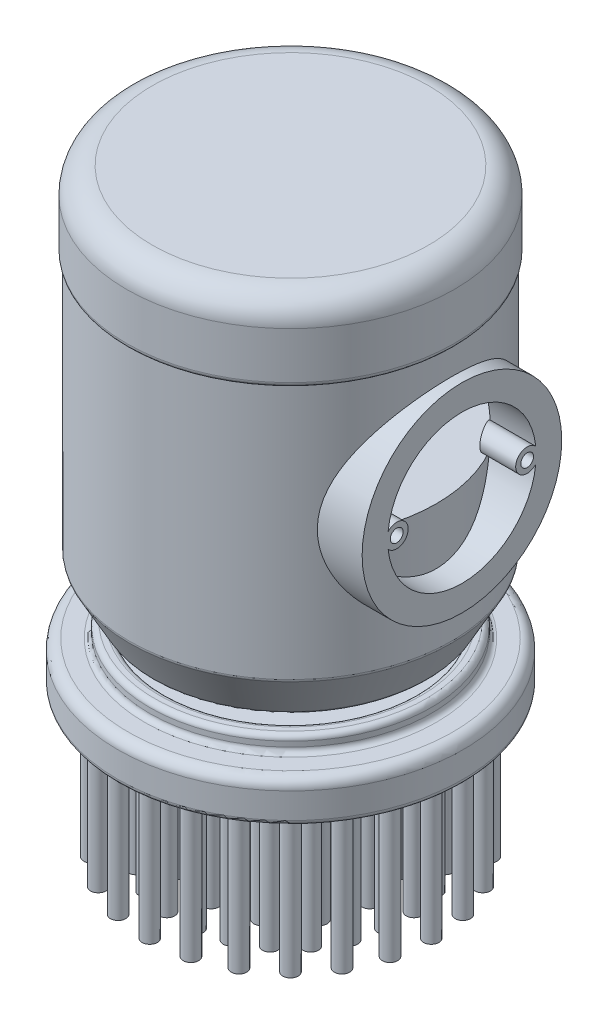
SolidWorks part; units mm, degrees
ref_plane "Front Plane" through (0, 0, 0) normal (0, 0, 1) x (1, 0, 0)
ref_plane "Top Plane" through (0, 0, 0) normal (0, 1, 0) x (1, 0, 0)
ref_plane "Right Plane" through (0, 0, 0) normal (1, 0, 0) x (0, 0, -1)
sketch "Sketch1" plane through (0, 0, 0) normal (0, 0, 1) x (1, 0, 0)
  line L0 (26.5, 0) -> (31.5, 9)
  line L1 (0, 0) -> (31.5, 0)
  line L2 (0, 0) -> (0, 74)
  line L3 (0, 74) -> (31.5, 74)
  line L4 (31.5, 0) -> (31.5, 74)
  line L6 (0, 0) -> (1.5, 0)
  line L7 (0, 0) -> (0, -3)
  line L8 (0, -3) -> (1.5, -3)
  line L9 (1.5, 0) -> (1.5, -3)
  line L10 (0, -3) -> (27.5, -3)
  line L11 (0, -3) -> (0, -6)
  line L12 (0, -6) -> (27.5, -6)
  line L13 (27.5, -3) -> (27.5, -6)
  line L14 (0, -6) -> (33.75, -6)
  line L15 (0, -6) -> (0, -14)
  line L16 (0, -14) -> (33.75, -14)
  line L17 (33.75, -6) -> (33.75, -14)
  dimension "D1" = 31.5
  dimension "D2" = 26.5
  dimension "D3" = 74
  dimension "D4" = 9
  dimension "D5" = 3
  dimension "D6" = 1.5
  dimension "D7" = 27.5
  dimension "D8" = 3
  dimension "D9" = 33.75
  dimension "D10" = 8
revolve "Revolve1" add sketch "Sketch1" angle 360 about L2 region at (15.6127, 37.3314, 0) region at (0.75, -1.5, 0) region at (13.75, -4.5, 0) region at (16.875, -10, 0)
sketch "Sketch2" plane through (0, -3, 0) normal (0, 1, 0) x (1, 0, 0)
  circle A0 centre (0, 0) radius 24.5
  circle A2 centre (0, 0) radius 13
  circle A3 centre (0, 0) radius 27.5 construction
  dimension "D1" = 3
  dimension "D2" = 26
extrude "Cut-Extrude2" cut sketch "Sketch2" against normal blind 2
sketch "Sketch5" plane through (0, 0, 0) normal (1, 0, 0) x (0, 0, -1)
  line L1 (31.5, 74) -> (-31.5, 74) construction
  circle A0 centre (0, 34.5) radius 19.5
  dimension "D1" = 39
  dimension "D2" = 39.5
extrude "Boss-Extrude3" add sketch "Sketch5" along normal blind 33.5
sketch "Sketch7" plane through (0, 74, 0) normal (0, 1, 0) x (1, 0, 0)
  circle A0 centre (0, 0) radius 28.5
  circle A1 centre (0, 0) radius 31.5 construction
  dimension "D1" = 3
extrude "Cut-Extrude3" cut sketch "Sketch7" against normal blind 43
sketch "Sketch3" plane through (0, 74, 0) normal (0, 1, 0) x (1, 0, 0)
  circle A0 centre (0, 0) radius 32
  dimension "D1" = 64
extrude "Boss-Extrude1" add sketch "Sketch3" against normal blind 15
sketch "Sketch4" plane through (0, -14, 0) normal (0, -1, 0) x (1, 0, 0)
  line L0 (0, 27.5) -> (0, 0) construction
  line L1 (0, 0) -> (7.1175, 26.563) construction
  line L2 (3.5895, 27.2647) -> (0, 0) construction
  line L3 (0, 21.6855) -> (2.8063, 21.3161)
  line L4 (2.8063, 21.3161) -> (5.6126, 20.9466)
  line L5 (0, 0) -> (2.8063, 21.3161) construction
  line L6 (0, 0) -> (8.2277, 19.8634) construction
  circle A0 centre (0, 0) radius 27.5 construction
  circle A1 centre (0, 27.5) radius 1.5
  circle A2 centre (0, 0) radius 21.5 construction
  circle A3 centre (0, 0) radius 15.5 construction
  circle A4 centre (0, 15.5) radius 1.5
  circle A5 centre (7.1175, 26.563) radius 1.5
  circle A6 centre (13.75, 23.8157) radius 1.5
  circle A7 centre (19.4454, 19.4454) radius 1.5
  circle A8 centre (23.8157, 13.75) radius 1.5
  circle A9 centre (26.563, 7.1175) radius 1.5
  circle A10 centre (27.5, 0) radius 1.5
  circle A11 centre (26.563, -7.1175) radius 1.5
  circle A12 centre (23.8157, -13.75) radius 1.5
  circle A13 centre (19.4454, -19.4454) radius 1.5
  circle A14 centre (13.75, -23.8157) radius 1.5
  circle A15 centre (7.1175, -26.563) radius 1.5
  circle A16 centre (0, -27.5) radius 1.5
  circle A17 centre (-7.1175, -26.563) radius 1.5
  circle A18 centre (-13.75, -23.8157) radius 1.5
  circle A19 centre (-19.4454, -19.4454) radius 1.5
  circle A20 centre (-23.8157, -13.75) radius 1.5
  circle A21 centre (-26.563, -7.1175) radius 1.5
  circle A22 centre (-27.5, 0) radius 1.5
  circle A23 centre (-26.563, 7.1175) radius 1.5
  circle A24 centre (-23.8157, 13.75) radius 1.5
  circle A25 centre (-19.4454, 19.4454) radius 1.5
  circle A26 centre (2.8063, 21.3161) radius 1.5
  circle A27 centre (0, 0) radius 9.5 construction
  circle A28 centre (-13.75, 23.8157) radius 1.5
  circle A29 centre (-7.1175, 26.563) radius 1.5
  circle A30 centre (8.2277, 19.8634) radius 1.5
  circle A31 centre (13.0884, 17.0571) radius 1.5
  circle A32 centre (17.0571, 13.0884) radius 1.5
  circle A33 centre (19.8634, 8.2277) radius 1.5
  circle A34 centre (21.3161, 2.8063) radius 1.5
  circle A35 centre (21.3161, -2.8063) radius 1.5
  circle A36 centre (19.8634, -8.2277) radius 1.5
  circle A37 centre (17.0571, -13.0884) radius 1.5
  circle A38 centre (13.0884, -17.0571) radius 1.5
  circle A39 centre (8.2277, -19.8634) radius 1.5
  circle A40 centre (2.8063, -21.3161) radius 1.5
  circle A41 centre (-2.8063, -21.3161) radius 1.5
  circle A42 centre (-8.2277, -19.8634) radius 1.5
  circle A43 centre (-13.0884, -17.0571) radius 1.5
  circle A44 centre (-17.0571, -13.0884) radius 1.5
  circle A45 centre (-19.8634, -8.2277) radius 1.5
  circle A46 centre (-21.3161, -2.8063) radius 1.5
  circle A47 centre (-21.3161, 2.8063) radius 1.5
  circle A48 centre (-19.8634, 8.2277) radius 1.5
  circle A49 centre (-17.0571, 13.0884) radius 1.5
  circle A50 centre (-13.0884, 17.0571) radius 1.5
  circle A51 centre (-8.2277, 19.8634) radius 1.5
  circle A52 centre (-2.8063, 21.3161) radius 1.5
  circle A53 centre (4.0117, 14.9719) radius 1.5
  circle A54 centre (7.75, 13.4234) radius 1.5
  circle A55 centre (10.9602, 10.9602) radius 1.5
  circle A56 centre (13.4234, 7.75) radius 1.5
  circle A57 centre (14.9719, 4.0117) radius 1.5
  circle A58 centre (15.5, 0) radius 1.5
  circle A59 centre (14.9719, -4.0117) radius 1.5
  circle A60 centre (13.4234, -7.75) radius 1.5
  circle A61 centre (10.9602, -10.9602) radius 1.5
  circle A62 centre (7.75, -13.4234) radius 1.5
  circle A63 centre (4.0117, -14.9719) radius 1.5
  circle A64 centre (0, -15.5) radius 1.5
  circle A65 centre (-4.0117, -14.9719) radius 1.5
  circle A66 centre (-7.75, -13.4234) radius 1.5
  circle A67 centre (-10.9602, -10.9602) radius 1.5
  circle A68 centre (-13.4234, -7.75) radius 1.5
  circle A69 centre (-14.9719, -4.0117) radius 1.5
  circle A70 centre (-15.5, 0) radius 1.5
  circle A71 centre (-14.9719, 4.0117) radius 1.5
  circle A72 centre (-13.4234, 7.75) radius 1.5
  circle A73 centre (-10.9602, 10.9602) radius 1.5
  circle A74 centre (-7.75, 13.4234) radius 1.5
  circle A75 centre (-4.0117, 14.9719) radius 1.5
  point P54 (0, 0)
  point P159 (0, 0)
  dimension "D1" = 6
  dimension "60" = 55
  dimension "D2" = 3
  dimension "D3" = 6
  dimension "D4" = 3
  dimension "D6" = 3
  dimension "D7" = 6
  dimension "D9" = 15
  dimension "D5" = 24
  dimension "D8" = 24
  dimension "D10" = 24
extrude "Boss-Extrude2" add sketch "Sketch4" along normal blind 29 contours A10 | A9 | A8 | A7 | A6 | A5 | A1 | A29 | A28 | A25 | A24 | A23 | A22 | A21 | A20 | A19 | A18 | A16 | A15 | A14 | A13 | A12 | A11 | A52 | A51 | A50 | A49 | A48 | A47 | A46 | A45 | A44 | A43 | A42 | A41 | A40 | A39 | A37 | A35 | A34 | A33 | A30 | L4 A26 L3 | L3 A26 L4 | A4 | A53 | A54 | A55 | A56 | A57 | A58 | A59 | A60 | A61 | A63 | A64 | A65 | A66 | A67 | A68 | A69 | A70 | A75 | A74 | A73 | A72 | A71 | A17 | A38 | A36 | A32 | A31 | A62 region at (2.8894, -14, 21.9472) region at (2.7232, -14, 20.6849) region at (0, -14, 27.5) region at (0, -14, 15.5) region at (7.1175, -14, 26.563) region at (13.75, -14, 23.8157) region at (19.4454, -14, 19.4454) region at (23.8157, -14, 13.75) region at (26.563, -14, 7.1175) region at (27.5, -14, 0) region at (26.563, -14, -7.1175) region at (23.8157, -14, -13.75) region at (19.4454, -14, -19.4454) region at (13.75, -14, -23.8157) region at (7.1175, -14, -26.563) region at (0, -14, -27.5) region at (-13.75, -14, -23.8157) region at (-19.4454, -14, -19.4454) region at (-23.8157, -14, -13.75) region at (-26.563, -14, -7.1175) region at (-27.5, -14, 0) region at (-26.563, -14, 7.1175) region at (-23.8157, -14, 13.75) region at (-19.4454, -14, 19.4454) region at (-13.75, -14, 23.8157) region at (-7.1175, -14, 26.563) region at (8.2277, -14, 19.8634) region at (19.8634, -14, 8.2277) region at (21.3161, -14, 2.8063) region at (21.3161, -14, -2.8063) region at (17.0571, -14, -13.0884) region at (8.2277, -14, -19.8634) region at (2.8063, -14, -21.3161) region at (-2.8063, -14, -21.3161) region at (-8.2277, -14, -19.8634) region at (-13.0884, -14, -17.0571) region at (-17.0571, -14, -13.0884) region at (-19.8634, -14, -8.2277) region at (-21.3161, -14, -2.8063) region at (-21.3161, -14, 2.8063) region at (-19.8634, -14, 8.2277) region at (-17.0571, -14, 13.0884) region at (-13.0884, -14, 17.0571) region at (-8.2277, -14, 19.8634) region at (-2.8063, -14, 21.3161) region at (4.0117, -14, 14.9719) region at (7.75, -14, 13.4234) region at (10.9602, -14, 10.9602) region at (13.4234, -14, 7.75) region at (14.9719, -14, 4.0117) region at (15.5, -14, 0) region at (14.9719, -14, -4.0117) region at (13.4234, -14, -7.75) region at (10.9602, -14, -10.9602) region at (4.0117, -14, -14.9719) region at (0, -14, -15.5) region at (-4.0117, -14, -14.9719) region at (-7.75, -14, -13.4234) region at (-10.9602, -14, -10.9602) region at (-13.4234, -14, -7.75)
fillet "Fillet1" radius 5 1 edges at (0, 74, 32)
fillet "Fillet2" radius 1 7 edges at (0, -3, 24.5) (0, -3, -27.5) (0, -14, -33.75) (0, -6, -27.5) (0, 0, -26.5) (0, 9, -31.5) (0, 59, 32)
fillet "Fillet3" radius 2 1 edges at (0, -6, -33.75)
sketch "Sketch6" plane through (33.5, 0, 0) normal (1, 0, 0) x (0, 0, -1)
  circle A0 centre (0, 34.5) radius 14.5
  circle A1 centre (0, 34.5) radius 19.5 construction
  dimension "D1" = 5
extrude "Cut-Extrude4" cut sketch "Sketch6" against normal up to surface (8.9643 mm away) up to face at (0, 31, 28.5)
sketch "Sketch9" plane through (0, 0, 0) normal (0, 0, 1) x (1, 0, 0)
  line L0 (33.5, 34.5) -> (24.7386, 34.5) construction
  line L1 (33.5, 15) -> (33.5, 54) construction
  spline S0 degree 2 poles (31.5, 15) (19.4286, 34.5) (31.5, 54) knots 0 0 0 1 1 1 weights 0.012 0.0315 0.051 construction
sketch "Sketch10" plane through (33.5, 0, 0) normal (1, 0, 0) x (0, 0, -1)
  line L0 (-19.5, 34.5) -> (19.5, 34.5) construction
  line L1 (0, 54) -> (0, 15) construction
  circle A0 centre (-12.75, 34.5) radius 2.25
  circle A1 centre (-12.75, 34.5) radius 1.25
  circle A2 centre (0, 34.5) radius 19.5 construction
  circle A5 centre (-12.75, 34.5) radius 1.75 construction
  circle A6 centre (0, 34.5) radius 14.5 construction
  circle A7 centre (12.75, 34.5) radius 2.25
  circle A8 centre (12.75, 34.5) radius 1.25
  dimension "D1" = 2.5
  dimension "D2" = 1
  dimension "D3" = 0.5
extrude "Boss-Extrude5" add sketch "Sketch10" against normal up to surface (7.0047 mm away) up to face at (-0.0136, 39.9732, 0.6225)
